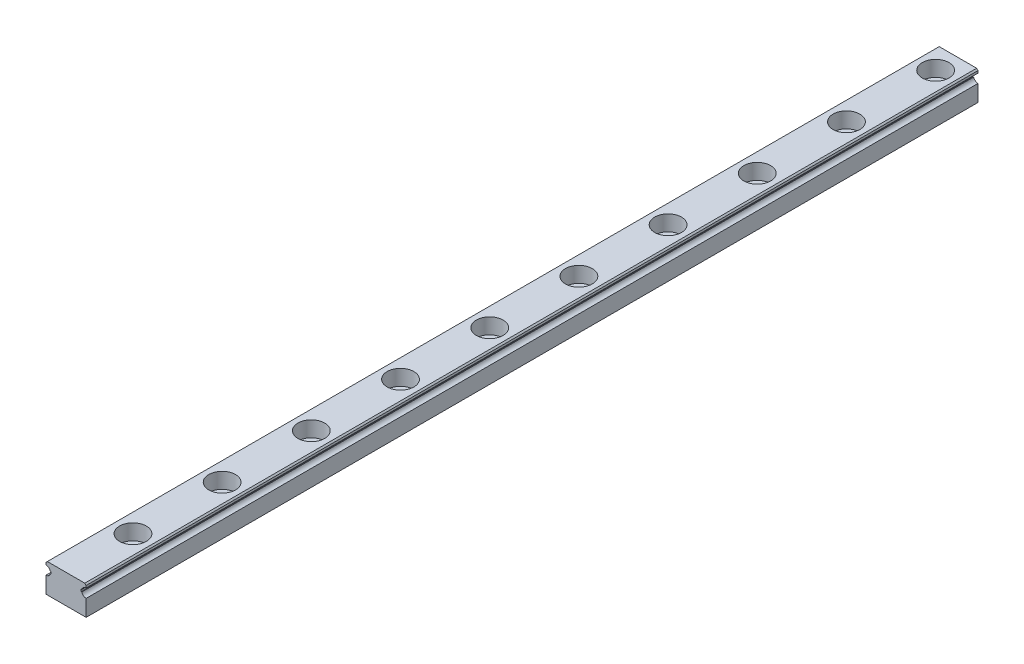
SolidWorks part; units mm, degrees
ref_plane "Спереди" through (0, 0, 0) normal (0, 0, 1) x (1, 0, 0)
ref_plane "Сверху" through (0, 0, 0) normal (0, 1, 0) x (1, 0, 0)
ref_plane "Справа" through (0, 0, 0) normal (1, 0, 0) x (0, 0, -1)
sketch "Sketch1" plane through (0, 0, 0) normal (0, 0, 1) x (1, 0, 0)
  line L0 (0, 0) -> (0, 5.7299) construction
  line L1 (-4.5, -3.25) -> (4.5, -3.25)
  line L2 (-4.5, -3.25) -> (-4.5, 0.45)
  line L3 (-4.5, 3.25) -> (4.5, 3.25)
  line L4 (4.5, -3.25) -> (4.5, 0.45)
  line L5 (-4.5, -3.25) -> (4.5, 3.25) construction
  line L6 (-4.5, 3.25) -> (4.5, -3.25) construction
  line L7 (-4.5, 2.45) -> (-4.5, 3.25)
  line L8 (-3.5318, 1.2) -> (-3.4, 1.2)
  line L9 (3.5318, 1.2) -> (3.4, 1.2)
  line L10 (-3.5318, 1.7) -> (-3.4, 1.7)
  line L11 (-3.4, 1.2) -> (-3.4, 1.7)
  line L12 (3.4, 1.2) -> (3.4, 1.7)
  line L13 (3.5318, 1.7) -> (3.4, 1.7)
  line L14 (4.5, 2.45) -> (4.5, 3.25)
  line L15 (-3.4, 1.45) -> (-4.5, 1.45) construction
  arc A0 (-3.5318, 1.7) -> (-4.5, 2.45) centre (-4.5, 1.45) ccw
  arc A1 (-4.5, 0.45) -> (-3.5318, 1.2) centre (-4.5, 1.45) ccw
  arc A2 (4.5, 0.45) -> (3.5318, 1.2) centre (4.5, 1.45) cw
  arc A3 (3.5318, 1.7) -> (4.5, 2.45) centre (4.5, 1.45) cw
  point P0 (0, 0)
  dimension "D3" = 1
  dimension "D1" = 9
  dimension "D2" = 6.5
  dimension "D4" = 2.05
  dimension "D5" = 6.8
  dimension "D6" = 0.5
extrude "Extrude1" add sketch "Sketch1" along normal blind 200
sketch "Sketch2" plane through (0, 3.25, 0) normal (0, 1, 0) x (1, 0, 0)
  line L0 (4.5, 0) -> (-4.5, 0) construction
  circle A0 centre (0, -5) radius 1.75
  circle A1 centre (0, -5) radius 3
  dimension "D1" = 3.5
  dimension "D2" = 6
  dimension "D3" = 5
extrude "Extrude2" cut sketch "Sketch2" against normal blind 3.5 contours A1
extrude "Extrude3" cut sketch "Sketch" against normal through all contours A0
sketch "Sketch" plane through (0, 3.25, 0) normal (0, 1, 0) x (1, 0, 0) same geometry as "Sketch2"
pattern_linear "LPattern1" count 40 spacing 20 along (0, 0, 1) of "Extrude2", "Extrude3"
chamfer "Chamfer1" distance 0.3 angle 45 2 edges at (4.5, 3.25, 100) (-4.5, 3.25, 100)
